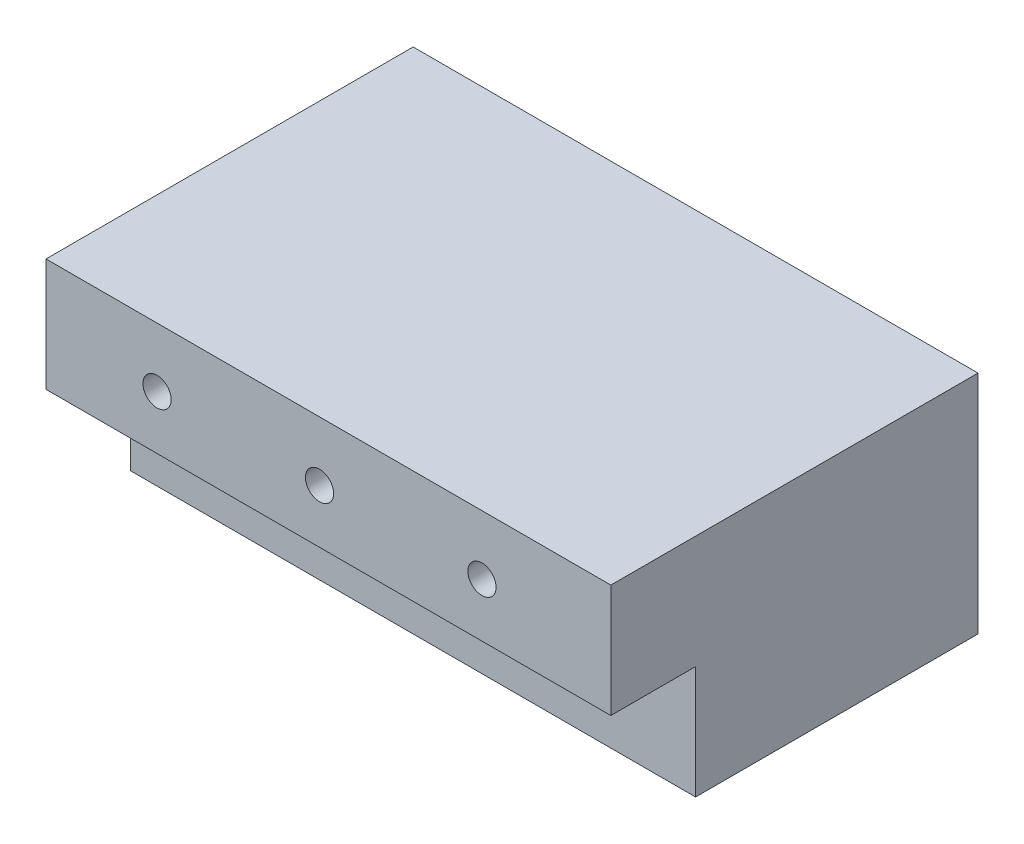
SolidWorks part; units mm, degrees
material "granite"
ref_plane "Front Plane" through (0, 0, 0) normal (0, 0, 1) x (1, 0, 0)
ref_plane "Top Plane" through (0, 0, 0) normal (0, 1, 0) x (1, 0, 0)
ref_plane "Right Plane" through (0, 0, 0) normal (1, 0, 0) x (0, 0, -1)
sketch "Эскиз1" plane through (0, 0, 0) normal (0, 0, 1) x (1, 0, 0)
  line L1 (0, 0) -> (200, 0)
  line L2 (0, 0) -> (0, 40)
  line L3 (0, 40) -> (200, 40)
  line L4 (200, 0) -> (200, 40)
  line L5 (0, 40) -> (200, 40)
  line L6 (0, 40) -> (0, 80)
  line L7 (0, 80) -> (200, 80)
  line L8 (200, 40) -> (200, 80)
extrude "Бобышка-Вытянуть1" add sketch "Эскиз1" along normal blind 100 contours L1 L4 L3 L2 region at (100, 20, 0)
extrude "Бобышка-Вытянуть2" add sketch "Эскиз1<3>" along normal blind 130 contours L3 L8 L7 L6 region at (100, 60, 0)
sketch "Эскиз1<3>" plane through (0, 0, 0) normal (0, 0, 1) x (1, 0, 0) same geometry as "Эскиз1"
sketch "Эскиз9" plane through (-3.1483, 38.9701, 130) normal (0, 0, 1) x (1, 0, 0)
  line L0 (0, 20) -> (200, 20)
  line L1 (0, 0) -> (0, 40) construction
  line L2 (200, 0) -> (200, 40) construction
  circle A0 centre (100, 20) radius 5
  circle A1 centre (42.4712, 20) radius 5
  circle A2 centre (157.5116, 20) radius 5
extrude "Вырез-Вытянуть4" cut sketch "Эскиз9" against normal blind 35 draft 1 contours A1
extrude "Вырез-Вытянуть5" cut sketch "Эскиз9<3>" against normal blind 25 draft 1 contours L0 A2 | L0 A2 region at (154.3633, 61.0922, 130) region at (154.3633, 56.8481, 130)
sketch "Эскиз9<3>" plane through (-3.1483, 38.9701, 130) normal (0, 0, 1) x (1, 0, 0) same geometry as "Эскиз9"
extrude "Вырез-Вытянуть6" cut sketch "Эскиз9<4>" against normal blind 30 draft 1 contours L0 A0 | L0 A0 region at (96.8517, 61.0922, 130) region at (96.8517, 56.8481, 130)
sketch "Эскиз9<4>" plane through (-3.1483, 38.9701, 130) normal (0, 0, 1) x (1, 0, 0) same geometry as "Эскиз9"
